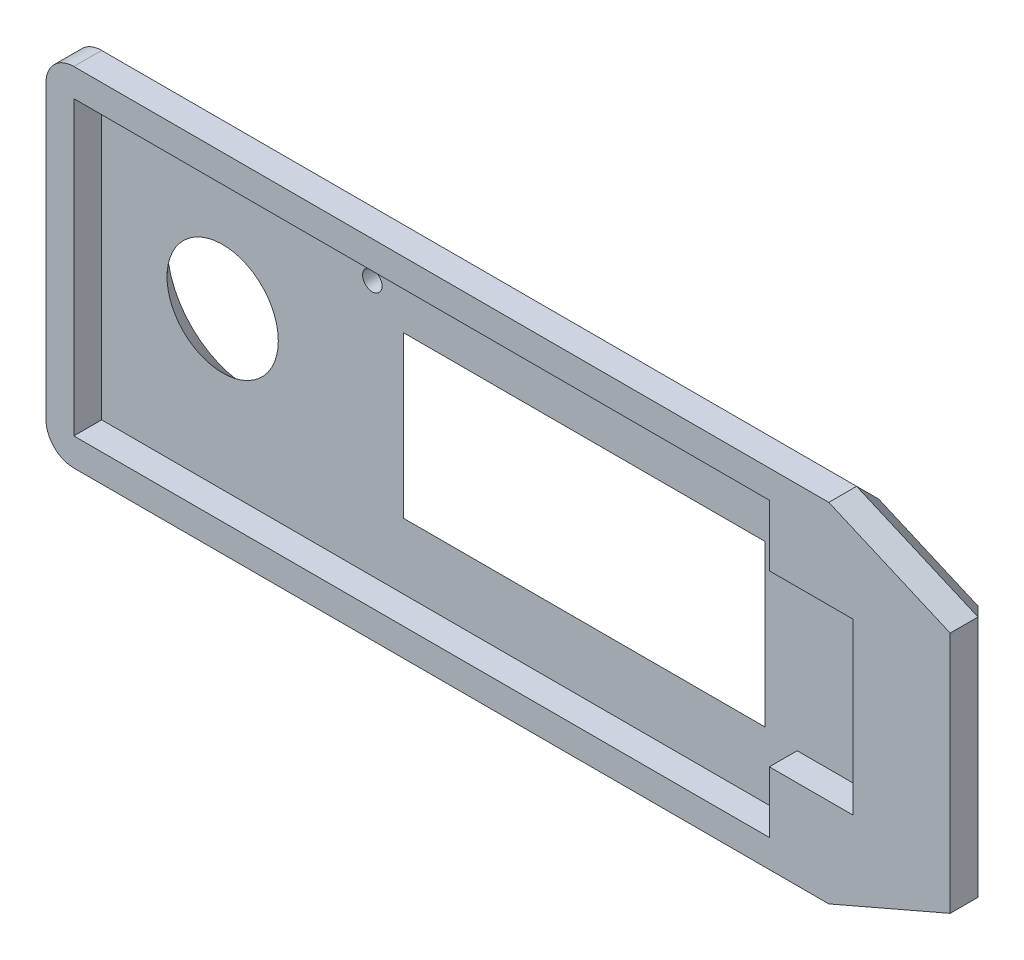
SolidWorks part; units mm, degrees
ref_plane "Спереди" through (0, 0, 0) normal (0, 0, 1) x (1, 0, 0)
ref_plane "Сверху" through (0, 0, 0) normal (0, 1, 0) x (1, 0, 0)
ref_plane "Справа" through (0, 0, 0) normal (1, 0, 0) x (0, 0, -1)
sketch "Эскиз1" plane through (0, 0, 0) normal (0, 0, 1) x (1, 0, 0)
  line L0 (-16.7031, 1.2008) -> (70.0547, 1.2008) construction
  line L1 (-16.7031, 11.7008) -> (33.2969, 11.7008) construction
  line L2 (-16.7031, 11.7008) -> (-16.7031, -9.2992) construction
  line L3 (-16.7031, -9.2992) -> (33.2969, -9.2992) construction
  line L4 (33.2969, 11.7008) -> (33.2969, -9.2992) construction
  line L5 (-16.7031, 11.7008) -> (33.2969, -9.2992) construction
  line L6 (-16.7031, -9.2992) -> (33.2969, 11.7008) construction
  line L7 (46.2969, 9.9258) -> (37.5703, 13.7008)
  line L8 (57.2969, 7.3008) -> (33.2969, 7.3008) construction
  line L9 (57.2969, 7.3008) -> (57.2969, -4.8992) construction
  line L10 (57.2969, -4.8992) -> (33.2969, -4.8992) construction
  line L11 (33.2969, 7.3008) -> (33.2969, -4.8992) construction
  line L12 (57.2969, 7.3008) -> (33.2969, -4.8992) construction
  line L13 (57.2969, -4.8992) -> (33.2969, 7.3008) construction
  line L14 (-18.7031, 13.7008) -> (37.5703, 13.7008)
  line L15 (-18.7031, 13.7008) -> (-18.7031, -11.2992)
  line L16 (-18.7031, -11.2992) -> (37.5703, -11.2992)
  line L17 (46.2969, 9.9258) -> (46.2969, -7.5242)
  line L20 (46.2969, -7.5242) -> (37.5703, -11.2992)
  point P4 (8.2969, 1.2008)
  point P7 (45.2969, 1.2008)
  point P12 (12.7969, 1.2008)
  dimension "D1" = 21
  dimension "D2" = 50
  dimension "D3" = 12.2
  dimension "D4" = 24
  dimension "D5" = 25
  dimension "D6" = 11
  dimension "D7" = 2
  dimension "D8" = 56.2734
extrude "Бобышка-Вытянуть1" add sketch "Эскиз1" along normal blind 2
sketch "Эскиз2" plane through (0, 0, 2) normal (0, 0, 1) x (1, 0, 0)
  line L0 (-18.7031, -11.2992) -> (37.5703, -11.2992) construction
  line L1 (-18.7031, 13.7008) -> (-18.7031, -11.2992) construction
  line L2 (46.2969, -7.5242) -> (46.2969, 9.9258) construction
  line L3 (37.5703, -11.2992) -> (46.2969, -7.5242) construction
  line L4 (-18.7031, -11.2992) -> (37.5703, -11.2992)
  line L5 (-18.7031, 13.7008) -> (-18.7031, -11.2992)
  line L6 (46.2969, -7.5242) -> (46.2969, 9.9258)
  line L7 (37.5703, -11.2992) -> (46.2969, -7.5242)
  line L8 (46.2969, 9.9258) -> (37.5703, 13.7008) construction
  line L9 (37.5703, 13.7008) -> (-18.7031, 13.7008) construction
  line L10 (46.2969, 9.9258) -> (37.5703, 13.7008)
  line L11 (37.5703, 13.7008) -> (-18.7031, 13.7008)
  line L12 (-16.7031, 1.2008) -> (49983.2969, 1.2008) construction
  line L13 (-16.7031, 11.7008) -> (33.2969, 11.7008)
  line L14 (-16.7031, 11.7008) -> (-16.7031, -9.2992)
  line L15 (-16.7031, -9.2992) -> (33.2969, -9.2992)
  line L16 (33.2969, 11.7008) -> (33.2969, 7.3008)
  line L17 (-16.7031, 11.7008) -> (33.2969, -9.2992) construction
  line L18 (-16.7031, -9.2992) -> (33.2969, 11.7008) construction
  line L19 (33.2969, -4.8992) -> (33.2969, -9.2992)
  line L20 (39.2969, -4.8992) -> (33.2969, -4.8992)
  line L21 (39.2969, -4.8992) -> (39.2969, 7.3008)
  line L22 (39.2969, 7.3008) -> (33.2969, 7.3008)
  line L24 (39.2969, -4.8992) -> (33.2969, 7.3008) construction
  line L25 (39.2969, 7.3008) -> (33.2969, -4.8992) construction
  point P10 (8.2969, 1.2008)
  point P13 (-16.7031, 1.2008)
  point P15 (36.2969, 1.2008)
  dimension "D1" = 2
  dimension "D2" = 2
  dimension "D3" = 2
  dimension "D4" = 50
  dimension "D5" = 12.2
  dimension "D6" = 6
extrude "Бобышка-Вытянуть2" add sketch "Эскиз2" along normal blind 2
sketch "Эскиз4" plane through (0, 0, 2) normal (0, 0, 1) x (1, 0, 0)
  line L0 (-8.0031, 9.3718) -> (-8.0031, -5.4361) construction
  line L1 (4.9969, 6.9758) -> (30.9969, 6.9758)
  line L2 (4.9969, 6.9758) -> (4.9969, -4.5742)
  line L3 (4.9969, -4.5742) -> (30.9969, -4.5742)
  line L4 (30.9969, 6.9758) -> (30.9969, -4.5742)
  line L5 (4.9969, 6.9758) -> (30.9969, -4.5742) construction
  line L6 (4.9969, -4.5742) -> (30.9969, 6.9758) construction
  line L7 (-16.7031, 1.2008) -> (39.2969, 1.2008) construction
  line L8 (-16.7031, 11.7008) -> (-16.7031, -9.2992) construction
  line L9 (39.2969, -4.8992) -> (39.2969, 7.3008) construction
  line L10 (46.2969, -7.5242) -> (46.2969, 9.9258) construction
  line L11 (-16.7031, 11.7008) -> (-16.7031, -9.2992) construction
  line L12 (-14.2179, 1.9008) -> (-1.2778, 1.9008) construction
  line L13 (33.2969, 11.7008) -> (-16.7031, 11.7008) construction
  circle A0 centre (-8.0031, 1.9679) radius 4
  circle A1 centre (2.7569, 9.1008) radius 0.7
  point P0 (17.9969, 1.2008)
  dimension "D6" = 8
  dimension "D7" = 1.4
  dimension "D1" = 11.55
  dimension "D2" = 26
  dimension "D3" = 15.3
  dimension "D4" = 8.7
  dimension "D5" = 9.8
  dimension "D8" = 2.6
  dimension "D9" = 19.46
extrude "Вырез-Вытянуть1" cut sketch "Эскиз4" against normal through all
chamfer "Фаска3" distance 2 angle 45 8 edges at (41.9336, 11.8133, 0) (46.2969, 1.2008, 0) (41.9336, -9.4117, 0) (-4.0031, 1.9679, 0) (30.9969, 1.2008, 0) (17.9969, -4.5742, 0) (4.9969, 1.2008, 0) (17.9969, 6.9758, 0)
fillet "Скругление2" radius 2 2 edges at (-18.7031, -11.2992, 2) (-18.7031, 13.7008, 2)
chamfer "Фаска4" distance 2 angle 45 5 edges at (7.9149, -11.2992, 0) (-18.1173, -10.7134, 0) (-18.7031, 1.2008, 0) (-18.1173, 13.115, 0) (7.9149, 13.7008, 0)
